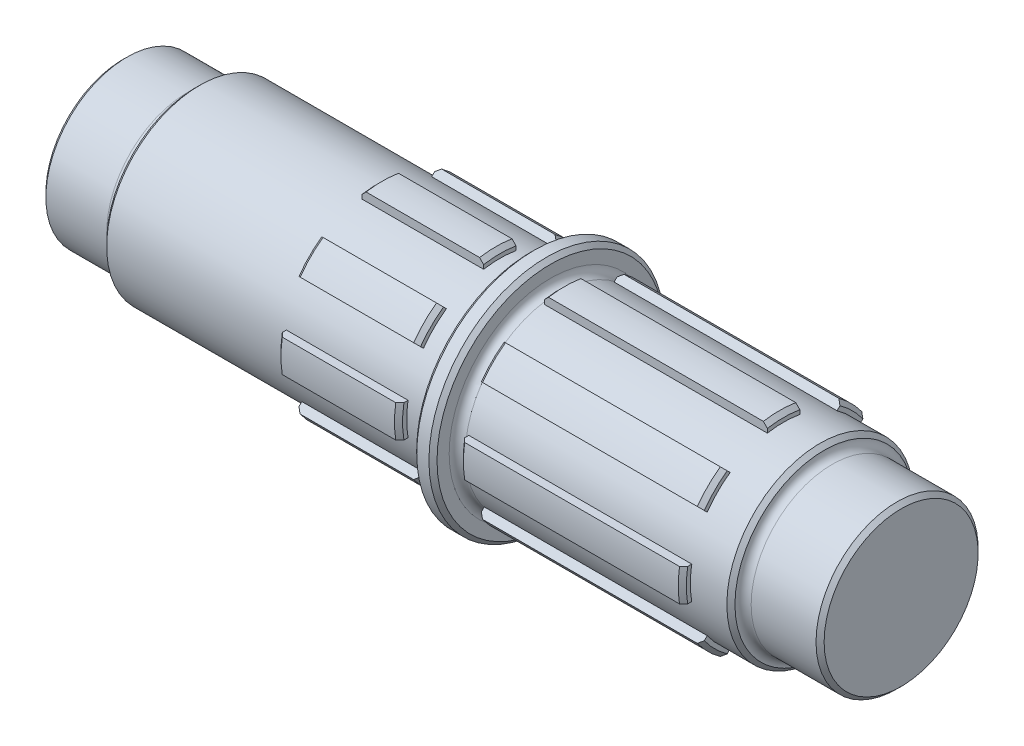
SolidWorks part; units mm, degrees
ref_plane "Front Plane" through (0, 0, 0) normal (0, 0, 1) x (1, 0, 0)
ref_plane "Top Plane" through (0, 0, 0) normal (0, 1, 0) x (1, 0, 0)
ref_plane "Right Plane" through (0, 0, 0) normal (1, 0, 0) x (0, 0, -1)
sketch "Sketch1" plane through (0, 0, 0) normal (0, 0, 1) x (1, 0, 0)
  line L0 (-133.4132, 0) -> (155.2096, 0) construction
  line L1 (-119.2814, 0) -> (-119.2814, 20)
  line L2 (-119.2814, 20) -> (-101.2814, 20)
  line L3 (-101.2814, 20) -> (-101.2814, 23)
  line L4 (-101.2814, 23) -> (-56.2814, 23)
  line L5 (-18.7814, 23) -> (-18.7814, 29)
  line L6 (-18.7814, 29) -> (-13.7814, 29)
  line L7 (-13.7814, 29) -> (-13.7814, 23)
  line L8 (-13.7814, 23) -> (-11.2814, 23)
  line L9 (53.7186, 23) -> (53.7186, 20)
  line L10 (53.7186, 20) -> (72.7186, 20)
  line L11 (72.7186, 20) -> (72.7186, 0)
  line L12 (-56.2814, 23) -> (-56.2814, 25)
  line L13 (-56.2814, 25) -> (-26.2814, 25)
  line L14 (-26.2814, 25) -> (-26.2814, 23)
  line L15 (-26.2814, 23) -> (-18.7814, 23)
  line L16 (-11.2814, 23) -> (-11.2814, 25)
  line L17 (-11.2814, 25) -> (43.7186, 25)
  line L18 (43.7186, 25) -> (43.7186, 23)
  line L19 (43.7186, 23) -> (53.7186, 23)
  line L20 (-119.2814, 0) -> (72.7186, 0)
  point P5 (-41.2814, 23)
  point P18 (16.2186, 23)
  dimension "D1" = 20
  dimension "D2" = 20
  dimension "D3" = 46
  dimension "D4" = 46
  dimension "D5" = 58
  dimension "D6" = 5
  dimension "D7" = 82.5
  dimension "D8" = 67.5
  dimension "D9" = 18
  dimension "D10" = 19
  dimension "D11" = 60
  dimension "D12" = 15
  dimension "D13" = 15
  dimension "D14" = 50
  dimension "D15" = 37.5
  dimension "D16" = 27.5
  dimension "D17" = 27.5
  dimension "D18" = 50
revolve "Revolve1" add sketch "Sketch1" angle 360 about L0
chamfer "Chamfer1" distance 1 angle 45 9 edges at (72.7186, 0, 20) (53.7186, 0, 23) (43.7186, 0, 25) (-13.7814, 0, 29) (-18.7814, 0, 29) (-26.2814, 0, 25) (-56.2814, 0, 25) (-101.2814, 0, 23) (-119.2814, 0, 20)
sketch "Sketch2" plane through (-56.2814, 0, 0) normal (-1, 0, 0) x (0, 0, 1)
  line L0 (0, 0) -> (0, 29.8061) construction
  line L1 (-4, 24.6779) -> (-4, 22.6495)
  line L2 (4, 24.6779) -> (4, 22.6495)
  line L3 (14.6215, 20.2784) -> (13.1872, 18.844)
  line L4 (20.2784, 14.6215) -> (18.844, 13.1872)
  line L5 (24.6779, 4) -> (22.6495, 4)
  line L6 (24.6779, -4) -> (22.6495, -4)
  line L7 (20.2784, -14.6215) -> (18.844, -13.1872)
  line L8 (14.6215, -20.2784) -> (13.1872, -18.844)
  line L9 (4, -24.6779) -> (4, -22.6495)
  line L10 (-4, -24.6779) -> (-4, -22.6495)
  line L11 (-14.6215, -20.2784) -> (-13.1872, -18.844)
  line L12 (-20.2784, -14.6215) -> (-18.844, -13.1872)
  line L13 (-24.6779, -4) -> (-22.6495, -4)
  line L14 (-24.6779, 4) -> (-22.6495, 4)
  line L15 (-20.2784, 14.6215) -> (-18.844, 13.1872)
  line L16 (-14.6215, 20.2784) -> (-13.1872, 18.844)
  circle A0 centre (0, 0) radius 25 construction
  circle A1 centre (0, 0) radius 23 construction
  arc A2 (-20.2784, 14.6215) -> (-24.6779, 4) centre (0, 0) ccw
  arc A3 (-18.844, 13.1872) -> (-22.6495, 4) centre (0, 0) ccw
  arc A4 (-24.6779, -4) -> (-20.2784, -14.6215) centre (0, 0) ccw
  arc A5 (-22.6495, -4) -> (-18.844, -13.1872) centre (0, 0) ccw
  arc A6 (-14.6215, -20.2784) -> (-4, -24.6779) centre (0, 0) ccw
  arc A7 (-13.1872, -18.844) -> (-4, -22.6495) centre (0, 0) ccw
  arc A8 (4, -24.6779) -> (14.6215, -20.2784) centre (0, 0) ccw
  arc A9 (4, -22.6495) -> (13.1872, -18.844) centre (0, 0) ccw
  arc A10 (20.2784, -14.6215) -> (24.6779, -4) centre (0, 0) ccw
  arc A11 (18.844, -13.1872) -> (22.6495, -4) centre (0, 0) ccw
  arc A12 (24.6779, 4) -> (20.2784, 14.6215) centre (0, 0) ccw
  arc A13 (22.6495, 4) -> (18.844, 13.1872) centre (0, 0) ccw
  arc A14 (14.6215, 20.2784) -> (4, 24.6779) centre (0, 0) ccw
  arc A15 (13.1872, 18.844) -> (4, 22.6495) centre (0, 0) ccw
  arc A16 (-4, 24.6779) -> (-14.6215, 20.2784) centre (0, 0) ccw
  arc A17 (-4, 22.6495) -> (-13.1872, 18.844) centre (0, 0) ccw
  point P42 (0, 0)
  dimension "D1" = 4
  dimension "D2" = 8
extrude "Cut-Extrude1" cut sketch "Sketch2" against normal up to surface (30 mm away) up to face at (-26.2814, 0, 24)
sketch "Sketch3" plane through (43.7186, 0, 0) normal (1, 0, 0) x (0, 0, -1)
  line L2 (-4, 22.6495) -> (-4, 24.6779)
  line L3 (-14.6215, 20.2784) -> (-13.1872, 18.844)
  line L4 (-4, 22.6495) -> (-4, 24.6779)
  line L5 (-14.6215, 20.2784) -> (-13.1872, 18.844)
  line L6 (4, -22.6495) -> (4, -24.6779)
  line L7 (14.6215, -20.2784) -> (13.1872, -18.844)
  line L8 (4, -22.6495) -> (4, -24.6779)
  line L9 (14.6215, -20.2784) -> (13.1872, -18.844)
  line L10 (-13.1872, -18.844) -> (-14.6215, -20.2784)
  line L11 (-4, -24.6779) -> (-4, -22.6495)
  line L12 (-13.1872, -18.844) -> (-14.6215, -20.2784)
  line L13 (-4, -24.6779) -> (-4, -22.6495)
  line L14 (-22.6495, -4) -> (-24.6779, -4)
  line L15 (-20.2784, -14.6215) -> (-18.844, -13.1872)
  line L16 (-22.6495, -4) -> (-24.6779, -4)
  line L17 (-20.2784, -14.6215) -> (-18.844, -13.1872)
  line L18 (-18.844, 13.1872) -> (-20.2784, 14.6215)
  line L19 (-24.6779, 4) -> (-22.6495, 4)
  line L20 (-18.844, 13.1872) -> (-20.2784, 14.6215)
  line L21 (-24.6779, 4) -> (-22.6495, 4)
  line L22 (13.1872, 18.844) -> (14.6215, 20.2784)
  line L23 (4, 24.6779) -> (4, 22.6495)
  line L24 (13.1872, 18.844) -> (14.6215, 20.2784)
  line L25 (4, 24.6779) -> (4, 22.6495)
  line L26 (22.6495, 4) -> (24.6779, 4)
  line L27 (20.2784, 14.6215) -> (18.844, 13.1872)
  line L28 (22.6495, 4) -> (24.6779, 4)
  line L29 (20.2784, 14.6215) -> (18.844, 13.1872)
  line L30 (18.844, -13.1872) -> (20.2784, -14.6215)
  line L31 (24.6779, -4) -> (22.6495, -4)
  line L32 (18.844, -13.1872) -> (20.2784, -14.6215)
  line L33 (24.6779, -4) -> (22.6495, -4)
  arc A2 (-4, 22.6495) -> (-13.1872, 18.844) centre (0, 0) ccw
  arc A3 (-4, 24.6779) -> (-14.6215, 20.2784) centre (0, 0) ccw
  arc A4 (-4, 22.6495) -> (-13.1872, 18.844) centre (0, 0) ccw
  arc A5 (-4, 24.6779) -> (-14.6215, 20.2784) centre (0, 0) ccw
  arc A6 (4, -22.6495) -> (13.1872, -18.844) centre (0, 0) ccw
  arc A7 (4, -24.6779) -> (14.6215, -20.2784) centre (0, 0) ccw
  arc A8 (4, -22.6495) -> (13.1872, -18.844) centre (0, 0) ccw
  arc A9 (4, -24.6779) -> (14.6215, -20.2784) centre (0, 0) ccw
  arc A10 (-13.1872, -18.844) -> (-4, -22.6495) centre (0, 0) ccw
  arc A11 (-14.6215, -20.2784) -> (-4, -24.6779) centre (0, 0) ccw
  arc A12 (-13.1872, -18.844) -> (-4, -22.6495) centre (0, 0) ccw
  arc A13 (-14.6215, -20.2784) -> (-4, -24.6779) centre (0, 0) ccw
  arc A14 (-22.6495, -4) -> (-18.844, -13.1872) centre (0, 0) ccw
  arc A15 (-24.6779, -4) -> (-20.2784, -14.6215) centre (0, 0) ccw
  arc A16 (-22.6495, -4) -> (-18.844, -13.1872) centre (0, 0) ccw
  arc A17 (-24.6779, -4) -> (-20.2784, -14.6215) centre (0, 0) ccw
  arc A18 (-18.844, 13.1872) -> (-22.6495, 4) centre (0, 0) ccw
  arc A19 (-20.2784, 14.6215) -> (-24.6779, 4) centre (0, 0) ccw
  arc A20 (-18.844, 13.1872) -> (-22.6495, 4) centre (0, 0) ccw
  arc A21 (-20.2784, 14.6215) -> (-24.6779, 4) centre (0, 0) ccw
  arc A22 (13.1872, 18.844) -> (4, 22.6495) centre (0, 0) ccw
  arc A23 (14.6215, 20.2784) -> (4, 24.6779) centre (0, 0) ccw
  arc A24 (13.1872, 18.844) -> (4, 22.6495) centre (0, 0) ccw
  arc A25 (14.6215, 20.2784) -> (4, 24.6779) centre (0, 0) ccw
  arc A26 (22.6495, 4) -> (18.844, 13.1872) centre (0, 0) ccw
  arc A27 (24.6779, 4) -> (20.2784, 14.6215) centre (0, 0) ccw
  arc A28 (22.6495, 4) -> (18.844, 13.1872) centre (0, 0) ccw
  arc A29 (24.6779, 4) -> (20.2784, 14.6215) centre (0, 0) ccw
  arc A30 (18.844, -13.1872) -> (22.6495, -4) centre (0, 0) ccw
  arc A31 (20.2784, -14.6215) -> (24.6779, -4) centre (0, 0) ccw
  arc A32 (18.844, -13.1872) -> (22.6495, -4) centre (0, 0) ccw
  arc A33 (20.2784, -14.6215) -> (24.6779, -4) centre (0, 0) ccw
  dimension "D1" = 0
  dimension "D2" = 0
  dimension "D3" = 0
  dimension "D4" = 0
  dimension "D5" = 0
  dimension "D6" = 0
  dimension "D7" = 0
  dimension "D8" = 0
chamfer "Chamfer2" distance 1 angle 45 1 edges at (-11.2814, 0, 25)
extrude "Cut-Extrude2" cut sketch "Sketch3" against normal up to surface (55 mm away) up to face at (-11.2814, 0, -24)
fillet "Fillet1" radius 2 4 edges at (53.7186, 0, 20) (-13.7814, 0, 23) (-18.7814, 0, 23) (-101.2814, 0, 20)
